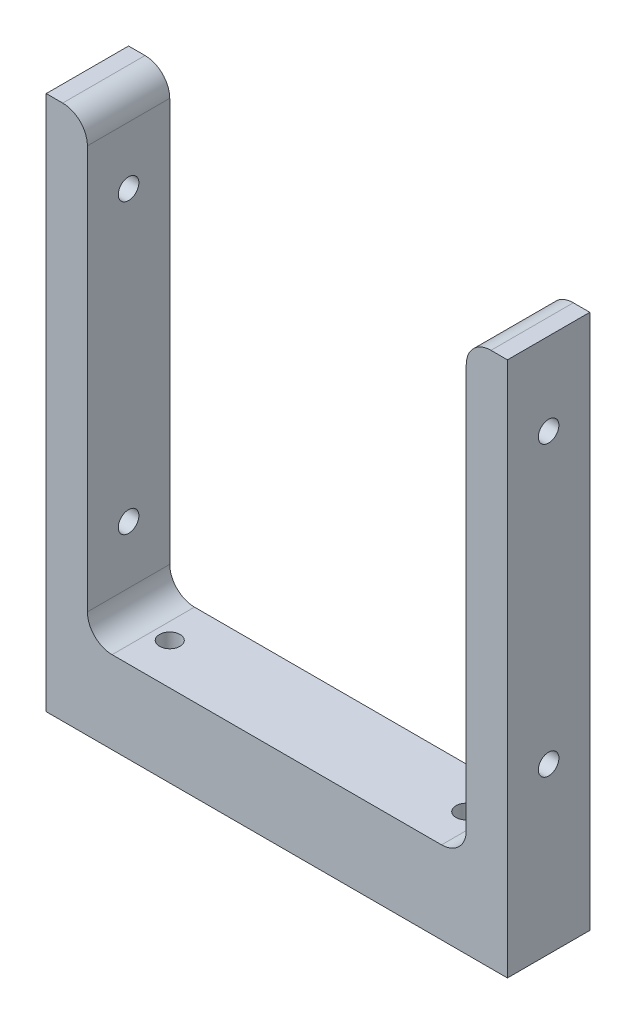
SolidWorks part; units mm, degrees
ref_plane "Спереди" through (0, 0, 0) normal (0, 0, 1) x (1, 0, 0)
ref_plane "Сверху" through (0, 0, 0) normal (0, 1, 0) x (1, 0, 0)
ref_plane "Справа" through (0, 0, 0) normal (1, 0, 0) x (0, 0, -1)
sketch "Эскиз1" plane through (0, 0, 0) normal (0, 0, 1) x (1, 0, 0)
  line L0 (28, 32.5) -> (23, 32.5)
  line L1 (-28, 32.5) -> (-23, 32.5)
  line L2 (-28, 32.5) -> (-28, -32.5)
  line L3 (-28, -32.5) -> (28, -32.5)
  line L4 (28, 32.5) -> (28, -32.5)
  line L5 (-28, 32.5) -> (28, -32.5) construction
  line L6 (-28, -32.5) -> (28, 32.5) construction
  line L7 (23, 32.5) -> (23, -22.5)
  line L8 (-23, -22.5) -> (23, -22.5)
  line L9 (-23, 32.5) -> (-23, -22.5)
  point P0 (0, 0)
  dimension "D1" = 56
  dimension "D2" = 65
  dimension "D3" = 5
  dimension "D4" = 10
  dimension "D5" = 5
extrude "Бобышка-Вытянуть1" add sketch "Эскиз1" along normal blind 10
fillet "Скругление1" radius 3 4 edges at (23, -22.5, 5) (-23, -22.5, 5) (-23, 32.5, 5) (23, 32.5, 5)
sketch "Эскиз2" plane through (0, -32.5, 0) normal (0, -1, 0) x (1, 0, 0)
  line L0 (-28, 5) -> (28, 5) construction
  line L1 (-28, 10) -> (-28, 0) construction
  line L2 (28, 10) -> (28, 0) construction
  line L3 (-18, 10) -> (-18, 0) construction
  line L4 (-28, 10) -> (28, 10) construction
  line L5 (-28, 0) -> (28, 0) construction
  line L6 (18, 10) -> (18, 0) construction
  dimension "D1" = 10
  dimension "D2" = 10
hole_wizard "Отверстие обработанное метчиком M3x0.51" positions "Эскиз4" profile "Эскиз3" tap size "M3x0.5" standard "Ansi Metric" end condition through all
sketch "Эскиз4" plane through (0, -32.5, 0) normal (0, -1, 0) x (-1, 0, 0)
  line L0 (18, -10) -> (18, 0) construction
  line L1 (-18, -10) -> (-18, 0) construction
  point P0 (18, -5)
  point P4 (-18, -5)
sketch "Эскиз3" plane through (-18, -32.5, 5) normal (1, 0, 0) x (0, 0, -1)
  line L0 (0, 0) -> (0, 65)
  line L1 (0, 65) -> (1.25, 65)
  line L2 (1.25, 65) -> (1.25, 0)
  line L5 (1.25, 0) -> (0, 0)
  line L11 (0, -6.35) -> (0, 107.95) construction
  dimension "Диаметр проходного сверла" = 2.5
  dimension "Глубина проходного сверла" = 65
cosmetic thread "Отверстие резьбы1" parameters "D2"=3
cosmetic thread "Отверстие резьбы2" parameters "D2"=3
sketch "Эскиз5" plane through (28, 0, 0) normal (1, 0, 0) x (0, 0, -1)
  line L0 (-5, 32.5) -> (-5, -32.5) construction
  line L1 (-10, 32.5) -> (0, 32.5) construction
  line L2 (-10, -32.5) -> (0, -32.5) construction
  line L3 (-6.8609, 22.5) -> (-1.9029, 22.5) construction
  line L4 (-2.7189, -12.5) -> (-7.8192, -12.5) construction
  dimension "D1" = 20
  dimension "D2" = 10
hole_wizard "Отверстие обработанное метчиком M3x0.52" positions "Эскиз7" profile "Эскиз6" tap size "M3x0.5" standard "Ansi Metric" end condition through all
sketch "Эскиз7" plane through (28, 0, 0) normal (1, 0, 0) x (0, 0, -1)
  line L0 (-5, 32.5) -> (-5, -32.5) construction
  line L1 (-6.8609, 22.5) -> (-1.9029, 22.5) construction
  line L2 (-2.7189, -12.5) -> (-7.8192, -12.5) construction
  point P0 (-5, 22.5)
  point P6 (-5, -12.5)
sketch "Эскиз6" plane through (28, 22.5, 5) normal (0, 1, 0) x (0, 0, -1)
  line L0 (0, 0) -> (0, 56)
  line L1 (0, 56) -> (1.25, 56)
  line L2 (1.25, 56) -> (1.25, 0)
  line L5 (1.25, 0) -> (0, 0)
  line L11 (0, -6.35) -> (0, 107.95) construction
  dimension "Диаметр проходного сверла" = 2.5
  dimension "Глубина проходного сверла" = 56
cosmetic thread "Отверстие резьбы3" parameters "D2"=3
cosmetic thread "Отверстие резьбы4" parameters "D2"=3
